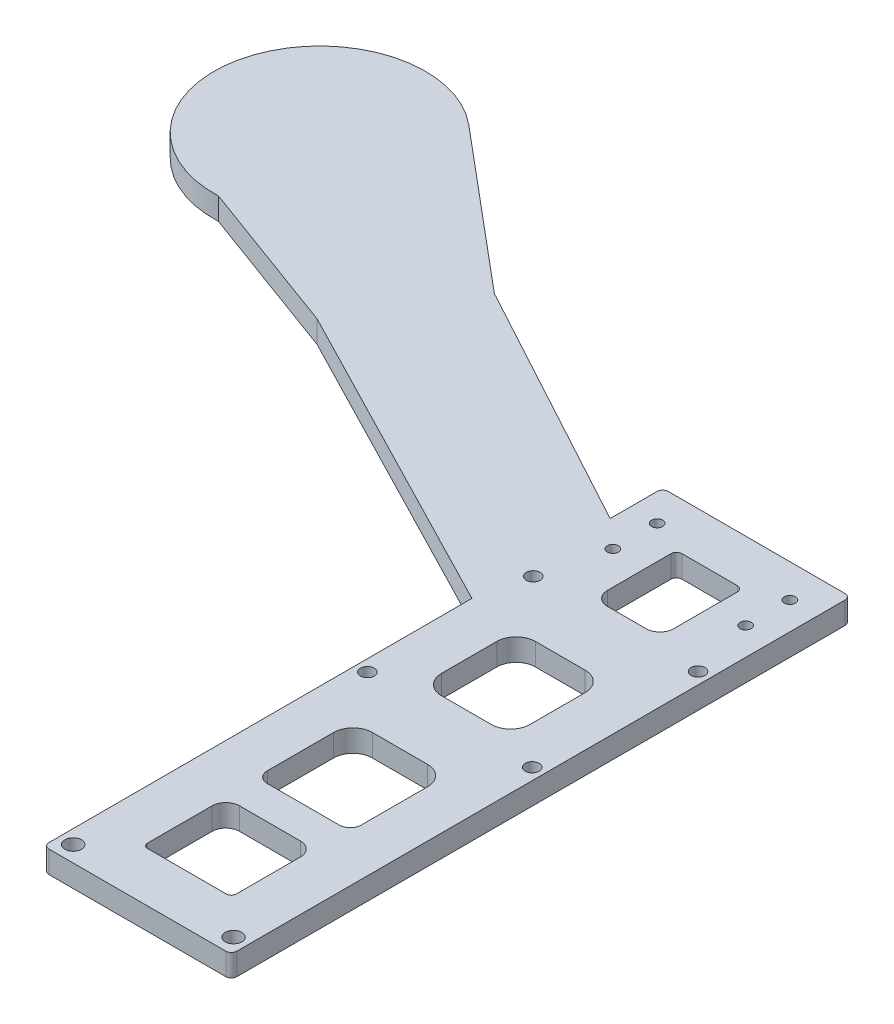
SolidWorks part; units mm, degrees
ref_plane "Front Plane" through (0, 0, 0) normal (0, 0, 1) x (1, 0, 0)
ref_plane "Top Plane" through (0, 0, 0) normal (0, 1, 0) x (1, 0, 0)
ref_plane "Right Plane" through (0, 0, 0) normal (1, 0, 0) x (0, 0, -1)
sketch "Frame Sketch" plane through (0, 0, 0) normal (0, 1, 0) x (1, 0, 0)
  line L0 (6.2981, 0.1404) -> (6.2981, 126.6085) construction
  line L6 (-10.7019, 46.6404) -> (-56.4191, 71.4182)
  line L11 (6.2981, 0.1404) -> (6.2981, -105.8001) construction
  line L23 (-9.7019, 56.1404) -> (22.2981, 56.1404)
  line L24 (-10.7019, 55.1404) -> (-10.7019, -54.8596)
  line L25 (-9.7019, -55.8596) -> (22.2981, -55.8596)
  line L26 (23.2981, 55.1404) -> (23.2981, -54.8596)
  line L27 (-10.7019, 56.1404) -> (23.2981, -55.8596) construction
  line L28 (-10.7019, -55.8596) -> (23.2981, 56.1404) construction
  line L44 (-0.8423, -46.8596) -> (13.4385, -46.8596)
  line L45 (-1.7019, -46) -> (-1.7019, -34.3596)
  line L46 (0.7981, -31.8596) -> (11.7981, -31.8596)
  line L47 (14.2981, -46) -> (14.2981, -34.3596)
  line L48 (-1.7019, -46.8596) -> (14.2981, -31.8596) construction
  line L49 (-1.7019, -31.8596) -> (14.2981, -46.8596) construction
  line L50 (12.7981, -25.8596) -> (-0.2019, -25.8596)
  line L51 (14.7981, -23.8596) -> (14.7981, -11.8596)
  line L52 (11.2981, -8.3596) -> (1.2981, -8.3596)
  line L53 (-2.2019, -23.8596) -> (-2.2019, -11.8596)
  line L54 (14.7981, -25.8596) -> (-2.2019, -8.3596) construction
  line L55 (14.7981, -8.3596) -> (-2.2019, -25.8596) construction
  line L56 (1.7981, 3.6404) -> (10.7981, 3.6404)
  line L57 (-1.7019, 7.1404) -> (-1.7019, 17.1404)
  line L58 (1.7981, 20.6404) -> (10.7981, 20.6404)
  line L59 (14.2981, 7.1404) -> (14.2981, 17.1404)
  line L60 (-1.7019, 3.6404) -> (14.2981, 20.6404) construction
  line L61 (-1.7019, 20.6404) -> (14.2981, 3.6404) construction
  line L62 (2.7981, 32.6404) -> (9.7981, 32.6404)
  line L63 (0.2981, 35.1404) -> (0.2981, 46.6404)
  line L64 (1.2981, 47.6404) -> (11.2981, 47.6404)
  line L65 (12.2981, 35.1404) -> (12.2981, 46.6404)
  line L66 (0.2981, 32.6404) -> (12.2981, 47.6404) construction
  line L67 (0.2981, 47.6404) -> (12.2981, 32.6404) construction
  line L88 (-10.7019, 21.6404) -> (-68.4798, 51.4182)
  line L89 (-10.7019, 40.5123) -> (-10.7019, -14.2315)
  line L91 (-10.7019, 46.6404) -> (-10.7019, 21.6404)
  line L92 (-56.4191, 71.4182) -> (-85.1457, 95.5228)
  line L94 (-68.4798, 51.4182) -> (-96.6434, 61.7532)
  arc A8 (23.2981, 55.1404) -> (22.2981, 56.1404) centre (22.2981, 55.1404) ccw
  arc A9 (23.2981, -54.8596) -> (22.2981, -55.8596) centre (22.2981, -54.8596) cw
  arc A10 (-9.7019, 56.1404) -> (-10.7019, 55.1404) centre (-9.7019, 55.1404) ccw
  arc A11 (-9.7019, -55.8596) -> (-10.7019, -54.8596) centre (-9.7019, -54.8596) cw
  circle A12 centre (-8.2019, -52.9596) radius 1.5
  circle A13 centre (20.7981, -52.9596) radius 1.5
  arc A14 (14.2981, -46) -> (13.4385, -46.8596) centre (13.4385, -46) cw
  arc A15 (-0.8423, -46.8596) -> (-1.7019, -46) centre (-0.8423, -46) cw
  arc A16 (-1.7019, -34.3596) -> (0.7981, -31.8596) centre (0.7981, -34.3596) cw
  arc A17 (11.7981, -31.8596) -> (14.2981, -34.3596) centre (11.7981, -34.3596) cw
  arc A18 (14.7981, -23.8596) -> (12.7981, -25.8596) centre (12.7981, -23.8596) cw
  arc A19 (-2.2019, -23.8596) -> (-0.2019, -25.8596) centre (-0.2019, -23.8596) ccw
  arc A20 (14.7981, -11.8596) -> (11.2981, -8.3596) centre (11.2981, -11.8596) ccw
  arc A21 (1.2981, -8.3596) -> (-2.2019, -11.8596) centre (1.2981, -11.8596) ccw
  arc A22 (1.7981, 3.6404) -> (-1.7019, 7.1404) centre (1.7981, 7.1404) cw
  arc A23 (14.2981, 7.1404) -> (10.7981, 3.6404) centre (10.7981, 7.1404) cw
  arc A24 (1.7981, 20.6404) -> (-1.7019, 17.1404) centre (1.7981, 17.1404) ccw
  arc A25 (14.2981, 17.1404) -> (10.7981, 20.6404) centre (10.7981, 17.1404) ccw
  arc A26 (2.7981, 32.6404) -> (0.2981, 35.1404) centre (2.7981, 35.1404) cw
  arc A27 (12.2981, 35.1404) -> (9.7981, 32.6404) centre (9.7981, 35.1404) cw
  arc A28 (1.2981, 47.6404) -> (0.2981, 46.6404) centre (1.2981, 46.6404) ccw
  arc A29 (12.2981, 46.6404) -> (11.2981, 47.6404) centre (11.2981, 46.6404) ccw
  circle A30 centre (18.2981, 50.1404) radius 1
  circle A31 centre (18.2981, 42.1404) radius 1
  circle A32 centre (-5.7019, 50.1404) radius 1
  circle A33 centre (-5.7019, 42.1404) radius 1
  circle A34 centre (-8.6019, 30.6404) radius 1.25
  circle A35 centre (-8.6019, 0.6404) radius 1.25
  circle A36 centre (21.1981, 0.6404) radius 1.25
  circle A37 centre (21.1981, 30.6404) radius 1.25
  arc A39 (-85.1457, 95.5228) -> (-96.6434, 61.7532) centre (-97.443, 80.8675) ccw
  point P0 (0, 0)
  point P6 (0, 0)
  point P17 (-33.5605, 59.0293)
  point P52 (6.2981, -39.3596)
  point P69 (6.2981, -17.1096)
  point P86 (6.2981, 12.1404)
  point P103 (6.2981, 40.1404)
  dimension "D6" = 9.5
  dimension "D7" = 2.9
  dimension "D8" = 2.5
  dimension "D5" = 17.5
  dimension "D11" = 9
  dimension "D12" = 9
  dimension "D13" = 12
  dimension "D14" = 52
  dimension "D17" = 25
  dimension "D18" = 20
  dimension "D19" = 65
  dimension "D20" = 37.5
  dimension "D23" = 30
  dimension "D25" = 1
  dimension "D30" = 6
  dimension "D31" = 6
  dimension "D32" = 8
  dimension "D36" = 2.5
  dimension "D38" = 2.1
  dimension "D3" = 112
  dimension "D4" = 34
  dimension "D9" = 15
  dimension "D10" = 16
  dimension "D15" = 17
  dimension "D16" = 6
  dimension "D21" = 17
  dimension "D22" = 16
  dimension "D27" = 12
  dimension "D28" = 15
  dimension "D29" = 12
extrude "Frame Bottom Plate" add sketch "Frame Sketch" along normal blind 4
